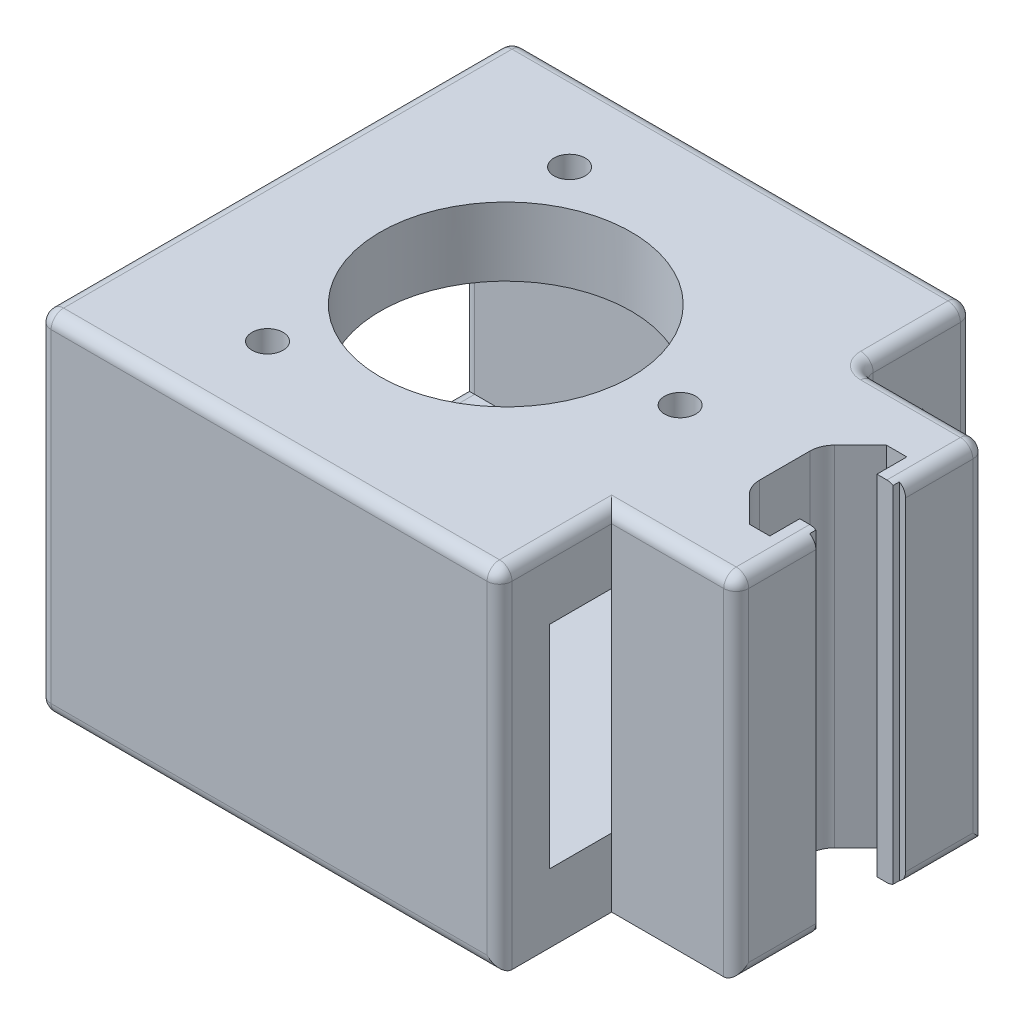
SolidWorks part; units mm, degrees
ref_plane "Front Plane" through (0, 0, 0) normal (0, 0, 1) x (1, 0, 0)
ref_plane "Top Plane" through (0, 0, 0) normal (0, 1, 0) x (1, 0, 0)
ref_plane "Right Plane" through (0, 0, 0) normal (1, 0, 0) x (0, 0, -1)
sketch "Sketch2" plane through (0, 0, 0) normal (1, 0, 0) x (0, 0, -1)
  line L0 (0, -8.5) -> (0, -24.413) construction
  line L1 (19, -14) -> (4, -14)
  line L2 (19, -14) -> (19, 14)
  line L3 (19, 14) -> (-19, 14)
  line L4 (-19, -14) -> (-19, 14)
  line L5 (19, -14) -> (-19, 14) construction
  line L6 (19, 14) -> (-19, -14) construction
  line L7 (-15, -8.5) -> (15, -8.5)
  line L8 (-15, -8.5) -> (-15, 8.5)
  line L9 (-15, 8.5) -> (15, 8.5)
  line L10 (15, -8.5) -> (15, 8.5)
  line L11 (-15, -8.5) -> (15, 8.5) construction
  line L12 (-15, 8.5) -> (15, -8.5) construction
  line L13 (0, -18) -> (-4, -14)
  line L14 (0, -18) -> (4, -14)
  line L15 (-4, -14) -> (-19, -14)
  point P0 (0, 0)
  point P5 (0, 0)
  dimension "D1" = 28
  dimension "D2" = 38
  dimension "D3" = 17
  dimension "D4" = 30
  dimension "D5" = 5.6569
  dimension "D6" = 45
extrude "Boss-Extrude1" add sketch "Sketch2" along normal blind 37
sketch "Sketch3" [suppressed] plane through (0, 14, 0) normal (0, 1, 0) x (1, 0, 0)
  line L0 (37, 19) -> (0, 19) construction
  line L1 (0, 0) -> (37, 0) construction
  line L2 (0, 19) -> (0, -19) construction
  line L3 (37, -19) -> (0, -19) construction
  line L4 (18.5, 19) -> (18.5, -19) construction
  line L5 (37, 19) -> (37, -19) construction
  circle A12 centre (11.5, 0) radius 6
  point P16 (18.5, 0)
  dimension "D1" = 7
  dimension "D5" = 12
extrude "Cut-Extrude1" [suppressed] cut sketch "Sketch3" against normal up to surface (5.5 mm away) contours A12 up to face at (18.5, 8.5, 0)
sketch "Sketch7" plane through (0, 14, 0) normal (0, 1, 0) x (1, 0, 0)
  line L0 (18.5, 19) -> (18.5, -19) construction
  line L1 (37, 19) -> (0, 19) construction
  line L2 (37, -19) -> (0, -19) construction
  circle A0 centre (18.5, 0) radius 10.075
  dimension "D1" = 20.15
extrude "Cut-Extrude4" cut sketch "Sketch7" against normal up to next
hole_wizard "M3x0.5 Tapped Hole1" positions "Sketch10" profile "Sketch9" tap size "M3x0.5" standard "ANSI Metric" end condition up to next
sketch "Sketch10" plane through (0, 14, 0) normal (0, 1, 0) x (1, 0, 0)
  line L0 (18.5, 19) -> (18.5, -19) construction
  line L1 (37, 19) -> (0, 19) construction
  line L2 (37, -19) -> (0, -19) construction
  line L3 (18.5, 0) -> (8.6233, 17.1069) construction
  circle A0 centre (18.5, 0) radius 14 construction
  point P12 (11.5, 12.1244)
  point P20 (32.5, 0)
  point P21 (11.5, -12.1244)
  dimension "D1" = 28
  dimension "D3" = 30
  dimension "D2" = 3
sketch "Sketch9" plane through (11.5, 14, 12.1244) normal (1, 0, 0) x (0, 0, 1)
  line L0 (0, 0) -> (0, 5.5)
  line L1 (0, 5.5) -> (1.25, 5.5)
  line L2 (1.25, 5.5) -> (1.25, 0)
  line L5 (1.25, 0) -> (0, 0)
  line L11 (0, -6.35) -> (0, 107.95) construction
  dimension "Thru Tap Drill Dia." = 2.5
  dimension "Thru Tap Drill Depth" = 5.5
cosmetic thread "Hole Thread1" parameters "D2"=3
cosmetic thread "Hole Thread2" parameters "D2"=3
cosmetic thread "Hole Thread3" parameters "D2"=3
sketch "Sketch4" [suppressed] plane through (0, 14, 0) normal (0, 1, 0) x (1, 0, 0)
  line L0 (0, 0) -> (37, 0) construction
  line L1 (37, 19) -> (37, -19) construction
  line L2 (18.5, 0) -> (1.119, 10.0349) construction
  circle A0 centre (18.5, 0) radius 15 construction
  circle A1 centre (5.5096, 7.5) radius 1.5
  circle A2 centre (18.5, 15) radius 1.5 [skipped]
  circle A3 centre (31.4904, 7.5) radius 1.5
  circle A4 centre (31.4904, -7.5) radius 1.5
  circle A5 centre (18.5, -15) radius 1.5 [skipped]
  circle A6 centre (5.5096, -7.5) radius 1.5
  dimension "D1" = 30
  dimension "D3" = 3
  dimension "D2" = 30
extrude "Cut-Extrude3" [suppressed] cut sketch "Sketch4" against normal up to next
sketch "Sketch6" plane through (0, -14, 0) normal (0, 1, 0) x (1, 0, 0)
  line L0 (37, 0) -> (55.0083, 0) construction
  line L1 (37, 19) -> (37, -19) construction
  line L2 (47, 19.1205) -> (47, -19.1205) construction
  line L3 (47, 3.6) -> (46.5, 3.6)
  line L4 (46.5, 3.6) -> (46.5, 3.1)
  line L5 (46.5, 3.1) -> (45.2, 3.1)
  line L6 (45.2, 3.1) -> (45.2, 5.5)
  line L7 (45.2, 5.5) -> (43.5607, 5.5)
  line L8 (37, 0) -> (50.5625, 13.5625) construction
  line L9 (41.4858, 3.4251) -> (43.5607, 5.5)
  line L10 (40.9, -2.0109) -> (40.9, 2.0109)
  line L11 (41.4858, -3.4251) -> (43.5607, -5.5)
  line L12 (45.2, -5.5) -> (43.5607, -5.5)
  line L13 (45.2, -3.1) -> (45.2, -5.5)
  line L14 (46.5, -3.1) -> (45.2, -3.1)
  line L15 (46.5, -3.6) -> (46.5, -3.1)
  line L16 (47, -3.6) -> (46.5, -3.6)
  line L17 (47, 10) -> (37, 10)
  line L18 (37, 10) -> (37, -10)
  line L19 (37, -10) -> (47, -10)
  line L20 (47, -10) -> (47, -3.6)
  line L21 (47, 10) -> (47, 3.6)
  arc A0 (40.9, 2.0109) -> (41.4858, 3.4251) centre (42.9, 2.0109) cw
  arc A1 (40.9, -2.0109) -> (41.4858, -3.4251) centre (42.9, -2.0109) ccw
  point P27 (40.9, 0)
  line M60 (37, 19) -> (37, 4)
  dimension "D9" = 2
  dimension "D1" = 10
  dimension "D2" = 0.5
  dimension "D3" = 1.8
  dimension "D4" = 7.2
  dimension "D5" = 6.2
  dimension "D6" = 11
  dimension "D7" = 45
  dimension "D8" = 1.5
  dimension "D10" = 3.9
  dimension "D11" = 20
extrude "Boss-Extrude2" add sketch "Sketch6" along normal up to surface (28 mm away) contours L6 L16 L15 L14 L13 | L10 A1 L11 L12 L13 L14 L15 L16 L20 L19 L18 L17 L21 L3 L4 L5 L6 L7 L9 A0 M60 region at (46.75, -14, -3.8236) up to face at (11.5, 14, -10.8744)
fillet "Fillet1" radius 1 28 edges at (42, 14, -10) (0, -8.5, 0) (0, 0, 15) (0, 8.5, 0) (0, 0, -15) (0, -14, 11.5) (0, -16, 2) (0, -16, -2) (0, -14, -11.5) (0, 14, 0) (18.5, -14, -19) (37, 0, -19) (18.5, 14, -19) (0, 0, -19) (18.5, 14, 19) (37, 0, 19) (18.5, -14, 19) (0, 0, 19) (37, 14, -14.5) (37, 11.25, -10) (42, 14, 10) (37, 14, 14.5) (47, 0, -10) (47, 0, 10) (47, -14, 6.8) (47, -14, -6.8) (47, 14, 6.8) (47, 14, -6.8)
